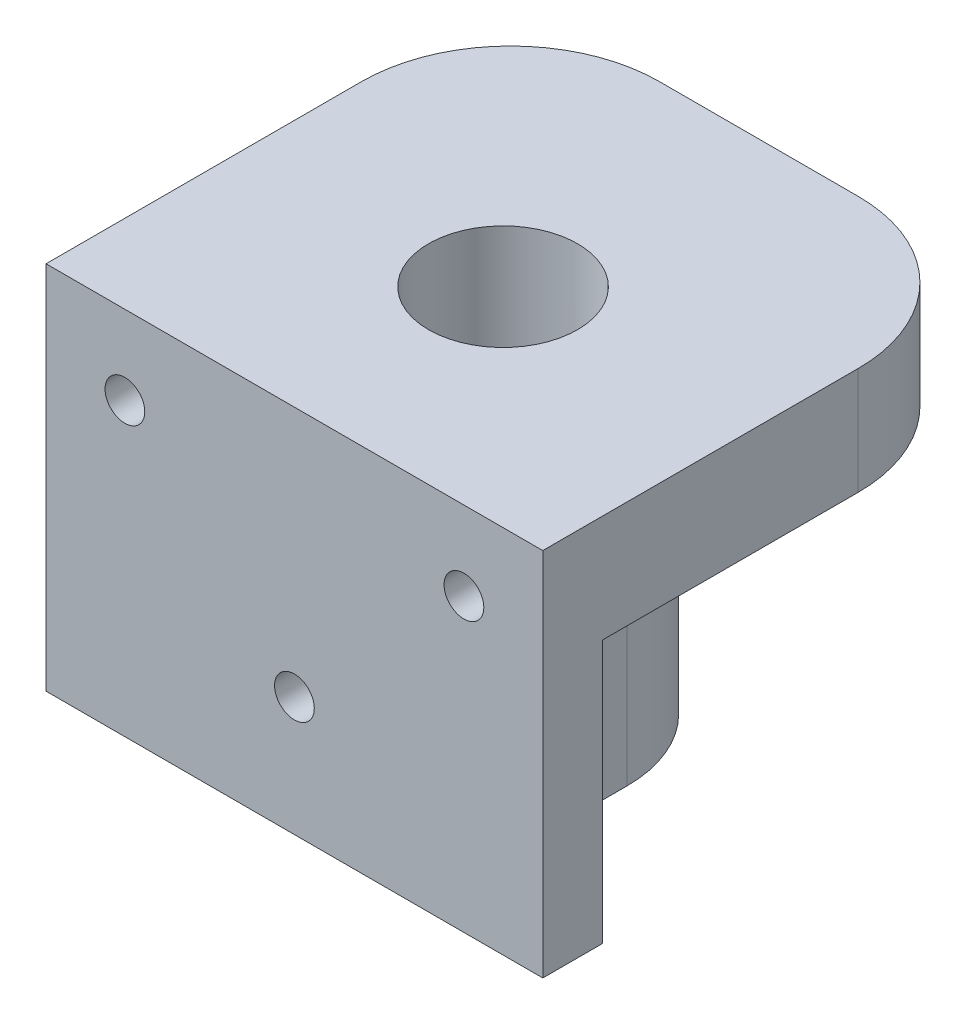
SolidWorks part; units mm, degrees
ref_plane "Front Plane" through (0, 0, 0) normal (0, 0, 1) x (1, 0, 0)
ref_plane "Top Plane" through (0, 0, 0) normal (0, 1, 0) x (1, 0, 0)
ref_plane "Right Plane" through (0, 0, 0) normal (1, 0, 0) x (0, 0, -1)
sketch "Profile-Sketch1" plane through (0, 0, 0) normal (0, 1, 0) x (1, 0, 0)
  line L0 (-25, -21) -> (25, -21)
  line L1 (25, -21) -> (25, -15)
  line L2 (-25, -21) -> (-25, -15)
  line L3 (-25, -15) -> (-22.5, -15)
  line L4 (-12.5, -5) -> (-12.5, 0)
  line L5 (25, -15) -> (22.5, -15)
  line L6 (12.5, -5) -> (12.5, 0)
  circle A0 centre (0, 0) radius 7.5
  arc A6 (12.5, 0) -> (-12.5, 0) centre (0, 0) ccw
  arc A7 (22.5, -15) -> (12.5, -5) centre (22.5, -5) cw
  arc A8 (-12.5, -5) -> (-22.5, -15) centre (-22.5, -5) cw
  dimension "D1" = 15
  dimension "D2" = 12.5
  dimension "D7" = 10
  dimension "D3" = 50
  dimension "D4" = 25
  dimension "D5" = 21
  dimension "D6" = 6
extrude "Profile-Boss-Extrude2" add sketch "Profile-Sketch1" along normal blind 37.2599
sketch "FasteningHoleSketch3" plane through (0, 0, 21) normal (0, 0, 1) x (1, 0, 0)
  line L0 (25, 37.2599) -> (25, 0) construction
  line L1 (-25, 37.2599) -> (-25, 0) construction
  line L2 (-25, 0) -> (25, 0) construction
  circle A2 centre (-17.0625, 29.3224) radius 2
  circle A3 centre (17.0625, 29.3224) radius 2
  dimension "D3" = 4
  dimension "D6" = 7.9375
  dimension "D2" = 29.3224
  dimension "D1" = 7.9375
extrude "FasteningHoleCut-Extrude8" cut sketch "FasteningHoleSketch3" against normal through all
sketch "LM8UUFasteningHoleSketch5" plane through (0, 0, 21) normal (0, 0, 1) x (1, 0, 0)
  line L0 (25, 37.2599) -> (25, 0) construction
  line L1 (-25, 0) -> (25, 0) construction
  line L2 (-25, 37.2599) -> (25, 37.2599) construction
  circle A0 centre (0, 12) radius 2
  circle A1 centre (-17.0625, 29.3224) radius 2 construction
  dimension "D1" = 25
  dimension "D2" = 12
  dimension "D3" = 25.2599
extrude "LM8UUFasteningHoleCut-Extrude9" cut sketch "LM8UUFasteningHoleSketch5" against normal through all
sketch "TopKnotchSketch2" plane through (0, 37.2599, 0) normal (0, 1, 0) x (1, 0, 0)
  line L0 (-25, -15) -> (25, -15)
  line L1 (-25, -15) -> (-25, 12.5)
  line L2 (25, -15) -> (25, 12.5)
  line L3 (-25, 12.5) -> (25, 12.5)
  line L4 (-25, -15) -> (-25, -21) construction
  arc A0 (12.5, 0) -> (-12.5, 0) centre (0, 0) ccw construction
extrude "TopKnotchCut-Extrude1" cut sketch "TopKnotchSketch2" against normal blind 10.8
sketch "TopShelfSketch3" plane through (0, 0, 15) normal (0, 0, -1) x (-1, 0, 0)
  line L0 (-25, 37.2599) -> (-25, 0) construction
  line L1 (-25, 37.2599) -> (25, 37.2599)
  line L2 (-25, 37.2599) -> (-25, 26.4599)
  line L3 (-25, 26.4599) -> (25, 26.4599)
  line L4 (25, 37.2599) -> (25, 26.4599)
  line L6 (22.5, 26.4599) -> (-22.5, 26.4599) construction
  line L7 (25, 37.2599) -> (25, 0) construction
  line L8 (-25, 37.2599) -> (25, 37.2599) construction
extrude "TopShelfBoss-Extrude1" add sketch "TopShelfSketch3" along normal blind 40.75
sketch "TopShelfLM8UUHoleSketch" plane through (0, 37.2599, 0) normal (0, 1, 0) x (1, 0, 0)
  circle A0 centre (0, 0) radius 7.5
  circle A1 centre (0, 0) radius 7.5 construction
extrude "TopShelfLM8UUCut-Extrude2" cut sketch "TopShelfLM8UUHoleSketch" against normal through all
fillet "Fillet3" radius 15 1 edges at (25, 31.8599, -25.75)
fillet "Fillet4" radius 15 1 edges at (-25, 31.8599, -25.75)
sketch "RightZAxisMicroSwitchSketch2" plane through (0, 0, 0) normal (0, -1, 0) x (1, 0, 0)
  line L0 (-12.5, 5) -> (-12.5, 0) construction
  line L1 (-11.1, 0) -> (-13.9, 0)
  line L2 (-11.1, 0) -> (-11.1, 12.85)
  line L3 (-11.1, 12.85) -> (-13.9, 12.85)
  line L5 (-13.9, 0) -> (-13.9, 10.086)
  line L6 (-13.9, 12.85) -> (-16.3426, 12.85)
  line L7 (-16.3426, 12.85) -> (-13.9, 10.086)
  dimension "D1" = 2.8
  dimension "D2" = 1.4
  dimension "D3" = 12.85
extrude "RightZAxisMicroSwitchCut-Extrude1" cut sketch "RightZAxisMicroSwitchSketch2" against normal blind 12.05
sketch "RightZAxisMicroSwitchMountingHoleSketch3" plane through (-11.1, 0, 0) normal (-1, 0, 0) x (0, 0, 1)
  line L0 (12.85, 12.05) -> (12.85, 0) construction
  line L1 (0, 26.4599) -> (0, 0) construction
  line L2 (0, 12.05) -> (12.85, 12.05) construction
  circle A0 centre (3.25, 5.05) radius 1.5
  circle A1 centre (9.6, 5.05) radius 1.5
  dimension "D1" = 3
  dimension "D2" = 3.25
  dimension "D3" = 3.25
  dimension "D4" = 7
extrude "RightZAxisMicroSwitchMountingHoleCut-Extrude1" cut sketch "RightZAxisMicroSwitchMountingHoleSketch3" against normal blind 3.1
equation "\"RailThickness\"= .125in'Spec"
equation "\"LM8UUDiameter\"= 15mm"
equation "\"MidLeftOrRightSideRailHeight\"= 2.0in"
equation "\"RodStabilizerLength\"= 50mm"
equation "\"HoleOffsetFromEdge\"= \"RailThickness\" * 2.5"
equation "\"StepperMountingHoleOffsetFromItsSide\"= 5.5mm'Spec"
equation "\"StepperMountingHoleOffsetFromLeftOrRightSide\"= \"StepperMountingHoleOffsetFromItsSide\" + \"RailThickness\""
equation "\"StepperMountingHoleDistance\"= 31mm'Spec"
equation "\"LM8UUHeight\"= 24mm'Spec"
equation "\"ZAxisLeadScrewLength\"= 200mm"
equation "\"LegHeight\"= 70mm'Space needed for PSU/Stepper/Electronics"
equation "\"V1 BottomOfLowerRail\"= \"LegHeight\""
equation "\"StepperShaftLength\"= 24mm'Pulley will be attached to the end"
equation "\"V2 ToBedAtTopOfZAxis\"= \"V1 BottomOfLowerRail\" - \"LowerEnclosureThickness\" + \"StepperShaftLength\" + \"ZAxisLeadScrewLength\" - \"LM8UUHeight\" / 2'Equals 277"
equation "\"HotEndToTopOfXAxisGB\"= 71.68487mm'Equals 71.68487. Measured after installed onto X-Axis linear rail guide block"
equation "\"TopOfGBToBottomOfLinearRail\"= \"LinearGBWidth\" / 2 + \"LinearRailWidth\" / 2'Equals 19.5"
equation "\"LinearGBWidth\"= 27mm'Spec"
equation "\"V5 ToBottomOfXAxisLinearRail\"= \"V4 ToTopOfBuildPlate/HotEndTip\" + \"HotEndToTopOfXAxisGB\" - \"TopOfGBToBottomOfLinearRail\"'Equals 352.18487"
equation "\"LinearRailWidth\"= 12mm'Spec"
equation "\"V6 ToMiddleOfYAxisGantryBlock\"= \"V5 ToBottomOfXAxisLinearRail\" - \"GABHeight\" / 2'Equals 334.18487"
equation "\"GABUpperHeight\"= 4mm"
equation "\"GABMidWallHeight\"= 28mm'Must equal 28 or changes alignment"
equation "\"BedToBuildPlateStandoffLength\"= 15mm"
equation "\"BuildPlateHeight\"= 8mm'Spec"
equation "\"V4 ToTopOfBuildPlate/HotEndTip\"= \"V2 ToBedAtTopOfZAxis\" + \"BedToBuildPlateStandoffLength\" + \"BuildPlateHeight\""
equation "\"RodStabilizerHeight\"= \"V8 ToBottomOfMidSideRail\" - \"V2 ToBedAtTopOfZAxis\" + \"HoleOffsetFromEdge\" * 2"
equation "\"LowerEnclosureThickness\"= 5mm"
equation "\"D1@Profile-Sketch1\" = \"LM8UUDiameter\""
equation "\"D3@Profile-Sketch1\" = \"RodStabilizerLength\""
equation "\"D4@Profile-Sketch1\" = \"RodStabilizerLength\" / 2"
equation "\"RodStabilizerWidthFromMidRailToZAxisRodCenter\"= \"StepperMountingHoleOffsetFromLeftOrRightSide\" + \"StepperMountingHoleDistance\" / 2 - \"RailThickness\""
equation "\"StandardWallThickness\"= 3mm"
equation "\"D6@Profile-Sketch1\" = \"StandardWallThickness\" * 2"
equation "\"D1@Profile-Boss-Extrude2\"= \"RodStabilizerHeight\""
equation "\"D6@FasteningHoleSketch3\"=\"HoleOffsetFromEdge\""
equation "\"D2@LM8UUFasteningHoleSketch5\"=\"LM8UUHeight\"/2"
equation "\"V8 ToTopOfMidSideRail\"= \"V6 ToMiddleOfYAxisGantryBlock\" + \"MidSideRailVerticalOffset\"'Equals 349.18487"
equation "\"D5@Profile-Sketch1\"=\"RodStabilizerWidthFromMidRailToZAxisRodCenter\""
equation "\"RodStabilizerMountingHoleYOffsetFromBottom\"= \"RodStabilizerHeight\" - \"HoleOffsetFromEdge\""
equation "\"D2@FasteningHoleSketch3\"=\"RodStabilizerMountingHoleYOffsetFromBottom\""
equation "\"D3@FasteningHoleSketch3\"=\"M3HeatInsertHoleDiameter\""
equation "\"GABLowerHeight\"= 4mm"
equation "\"GABHeight\"= \"GABLowerHeight\" + \"GABMidWallHeight\" + \"GABUpperHeight\""
equation "\"V8 ToBottomOfMidSideRail\"= \"V8 ToTopOfMidSideRail\" - \"MidLeftOrRightSideRailHeight\"'Equals 298.38487"
equation "\"D1@LM8UUFasteningHoleSketch5\"=\"RodStabilizerLength\"/2"
equation "\"MidSideRailVerticalOffset\"= \"LinearRailWidth\" + 3mm'Allows space for RodStabilizer to attach to bottom of MidSideRail"
equation "\"M3HeatInsertHoleDiameter\"= 4mm'Spec"
equation "\"MicroSwitchLength\"= 12.85mm"
equation "\"MicroSwitchHeight\"= 6.55mm"
equation "\"MicroSwitchMountHoleOffsetFromSide\"= 3.25mm"
equation "\"MicroSwitchDepth\"= 2.8mm"
equation "\"MicroSwitchTerminalHeight\"= 3.5mm"
equation "\"M2HeatInsertHoleDiameter\"= 3mm'Spec"
equation "\"MicroSwitchMountHoleOffsetFromBottom\"= 1.5mm"
equation "\"MicroSwitchExtraMountingHeight\"= 2mm"
equation "\"M2HeatInsertHoleDepth\"= 3.1mm'Spec"
equation "\"GABDistanceFromBackToFirstPulley\"= 13.5mm"
equation "\"GABPulleyDDistanceBetween\"= 12.5mm'From the100"
equation "\"GABDistanceFromPulleyToFront\"= 8mm"
equation "\"GABDepth\"= \"GABDistanceFromBackToFirstPulley\" + \"GABPulleyDDistanceBetween\" + \"GABDistanceFromPulleyToFront\""
equation "\"LinearGBWithRailDepth\"= 12.75mm'Spec"
equation "\"GABDepthPlusLinearRail\"= \"GABDepth\" + \"LinearGBWithRailDepth\""
equation "\"D1@TopKnotchCut-Extrude1\" = \"MicroSwitchDepth\" + 8mm"
equation "\"D1@TopShelfBoss-Extrude1\" = \"GABDepthPlusLinearRail\" - \"StandardWallThickness\" * 2"
equation "\"D1@Fillet3\"=\"LM8UUDiameter\""
equation "\"D1@Fillet4\"=\"LM8UUDiameter\""
equation "\"D1@RightZAxisMicroSwitchSketch2\" = \"MicroSwitchDepth\""
equation "\"D2@RightZAxisMicroSwitchSketch2\" = \"MicroSwitchDepth\" / 2"
equation "\"D3@RightZAxisMicroSwitchSketch2\" = \"MicroSwitchLength\""
equation "\"D1@RightZAxisMicroSwitchCut-Extrude1\"=\"MicroSwitchHeight\" + \"MicroSwitchTerminalHeight\" + \"MicroSwitchExtraMountingHeight\""
equation "\"D1@RightZAxisMicroSwitchMountingHoleCut-Extrude1\" = \"M2HeatInsertHoleDepth\""
equation "\"D1@RightZAxisMicroSwitchMountingHoleSketch3\"=\"M2HeatInsertHoleDiameter\""
equation "\"D2@RightZAxisMicroSwitchMountingHoleSketch3\"=\"MicroSwitchMountHoleOffsetFromSide\""
equation "\"D3@RightZAxisMicroSwitchMountingHoleSketch3\"=\"MicroSwitchMountHoleOffsetFromSide\""
equation "\"D4@RightZAxisMicroSwitchMountingHoleSketch3\"=\"MicroSwitchExtraMountingHeight\" + \"MicroSwitchTerminalHeight\" + \"MicroSwitchMountHoleOffsetFromBottom\""
